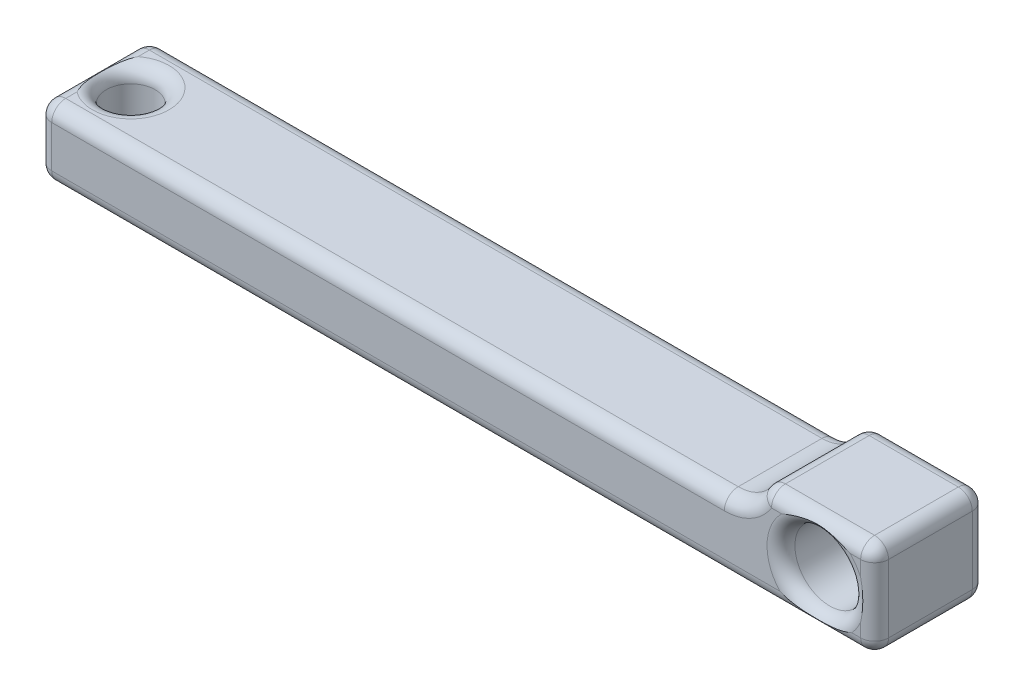
SolidWorks part; units mm, degrees
ref_plane "Front Plane" through (0, 0, 0) normal (0, 0, 1) x (1, 0, 0)
ref_plane "Top Plane" through (0, 0, 0) normal (0, 1, 0) x (1, 0, 0)
ref_plane "Right Plane" through (0, 0, 0) normal (1, 0, 0) x (0, 0, -1)
sketch "Sketch1" plane through (0, 0, 0) normal (0, 0, 1) x (1, 0, 0)
  line L0 (0, 0) -> (-22273.8271, 0) construction
  line L2 (-33.6905, 2.5) -> (26.3095, 2.5)
  line L3 (-33.6905, 2.5) -> (-33.6905, -2.5)
  line L4 (-33.6905, -2.5) -> (26.3095, -2.5)
  line L5 (26.3095, 2.5) -> (26.3095, -2.5)
  dimension "D1" = 5
  dimension "D2" = 2.5
  dimension "D3" = 60
extrude "Boss-Extrude1" add sketch "Sketch1" against normal blind 8
sketch "Sketch4" plane through (0, 2.5, 0) normal (0, 1, 0) x (1, 0, 0)
  line L0 (26.3095, 0) -> (-33.6905, 0) construction
  circle A0 centre (-31.0251, 4) radius 1.75
  dimension "D2" = 3.5
  dimension "D1" = 4
extrude "Cut-Extrude2" cut sketch "Sketch4" against normal through all
sketch "Sketch11" plane through (0, 0, -8) normal (0, 0, -1) x (-1, 0, 0)
  line L0 (-26.3095, 2.5) -> (33.6905, 2.5) construction
  line L1 (-18.3095, 2.5) -> (-26.3095, 2.5)
  line L2 (-18.3095, 2.5) -> (-18.3095, 4.3692)
  line L3 (-18.3095, 4.3692) -> (-26.3095, 4.3692)
  line L4 (-26.3095, 2.5) -> (-26.3095, 4.3692)
  dimension "D1" = 8
extrude "Boss-Extrude4" add sketch "Sketch11" against normal blind 8
fillet "Fillet4" radius 3 1 edges at (18.3095, 2.5, -4)
sketch "Sketch12" plane through (0, 0, -8) normal (0, 0, -1) x (-1, 0, 0)
  line L0 (-18.3095, 4.3692) -> (-26.3095, 4.3692) construction
  circle A0 centre (-22.0943, 0.8692) radius 2.5
  dimension "D1" = 5
  dimension "D2" = 3.5
extrude "Cut-Extrude6" cut sketch "Sketch12" against normal through all
sketch "Sketch13" plane through (0, -2.5, 0) normal (0, -1, 0) x (1, 0, 0)
  line L0 (-33.6905, 0) -> (26.3095, 0) construction
  circle A0 centre (15.4101, -4) radius 1.75
  dimension "D1" = 3.5
  dimension "D2" = 4
extrude "Cut-Extrude7" cut sketch "Sketch13" against normal blind 3
fillet "Fillet5" radius 1 22 edges at (-31.0251, -2.5, -2.25) (17.1601, -2.5, -4) (26.3095, -2.5, -4) (26.3095, 4.3692, -4) (18.3095, 4.3692, -4) (-3.6905, -2.5, -8) (26.3095, 0.9346, -8) (22.3095, 4.3692, -8) (17.2053, 3.0108, -8) (19.5943, 0.8692, -8) (-33.6905, -2.5, -4) (-33.6905, 0, -8) (-33.6905, 2.5, -4) (-9.0798, 2.5, -8) (-31.0251, 2.5, -2.25) (-9.0798, 2.5, 0) (17.2053, 3.0108, 0) (22.3095, 4.3692, 0) (26.3095, 0.9346, 0) (-3.6905, -2.5, 0) (-33.6905, 0, 0) (19.5943, 0.8692, 0)
